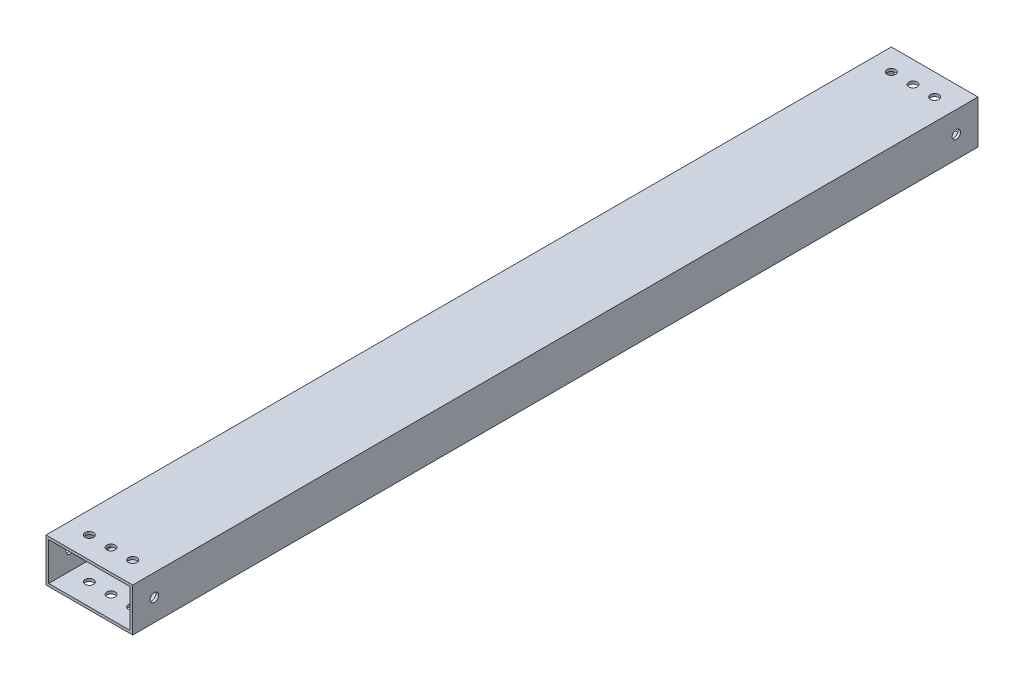
SolidWorks part; units mm, degrees
material "6061-T6 (SS)"
ref_plane "Front Plane" through (0, 0, 0) normal (0, 0, 1) x (1, 0, 0)
ref_plane "Top Plane" through (0, 0, 0) normal (0, 1, 0) x (1, 0, 0)
ref_plane "Right Plane" through (0, 0, 0) normal (1, 0, 0) x (0, 0, -1)
sketch "Sketch1" plane through (0, 0, 0) normal (0, 0, 1) x (1, 0, 0)
  line L0 (-23.8125, 11.1125) -> (23.8125, 11.1125)
  line L1 (-25.4, -12.7) -> (25.4, -12.7)
  line L2 (-25.4, -12.7) -> (-25.4, 12.7)
  line L3 (-25.4, 12.7) -> (25.4, 12.7)
  line L4 (25.4, -12.7) -> (25.4, 12.7)
  line L5 (-25.4, -12.7) -> (25.4, 12.7) construction
  line L6 (-25.4, 12.7) -> (25.4, -12.7) construction
  line L7 (23.8125, -11.1125) -> (23.8125, 11.1125)
  line L8 (-23.8125, -11.1125) -> (23.8125, -11.1125)
  line L9 (-23.8125, -11.1125) -> (-23.8125, 11.1125)
  point P0 (0, 0)
  dimension "D1" = 50.8
  dimension "D2" = 25.4
  dimension "D3" = 1.5875
extrude "Boss-Extrude1" add sketch "Sketch1" along normal mid plane 495.3
sketch "Sketch2" plane through (0, 12.7, 0) normal (0, 1, 0) x (1, 0, 0)
  line L0 (25.4, 247.65) -> (-25.4, 247.65) construction
  line L1 (-25.4, 0) -> (25.4, 0) construction
  line L2 (-25.4, -247.65) -> (-25.4, 247.65) construction
  line L3 (25.4, -247.65) -> (25.4, 247.65) construction
  circle A0 centre (-12.7, 234.95) radius 2.4892
  circle A1 centre (0, 234.95) radius 2.4892
  circle A2 centre (12.7, 234.95) radius 2.4892
  circle A3 centre (12.7, -234.95) radius 2.4892
  circle A4 centre (0, -234.95) radius 2.4892
  circle A5 centre (-12.7, -234.95) radius 2.4892
  point P9 (0, 247.65)
  dimension "D1" = 4.9784
  dimension "D2" = 12.7
  dimension "D3" = 12.7
  dimension "D4" = 12.7
extrude "Cut-Extrude1" cut sketch "Sketch2" against normal through all
sketch "Sketch3" plane through (25.4, 0, 0) normal (1, 0, 0) x (0, 0, -1)
  line L0 (247.65, -12.7) -> (247.65, 12.7) construction
  line L1 (0, 12.7) -> (0, -12.7) construction
  line L2 (-247.65, 12.7) -> (247.65, 12.7) construction
  line L3 (-247.65, -12.7) -> (247.65, -12.7) construction
  circle A0 centre (234.95, 0) radius 2.4892
  circle A1 centre (-234.95, 0) radius 2.4892
  point P5 (247.65, 0)
  dimension "D1" = 12.7
  dimension "D2" = 4.9784
extrude "Cut-Extrude2" cut sketch "Sketch3" against normal through all
